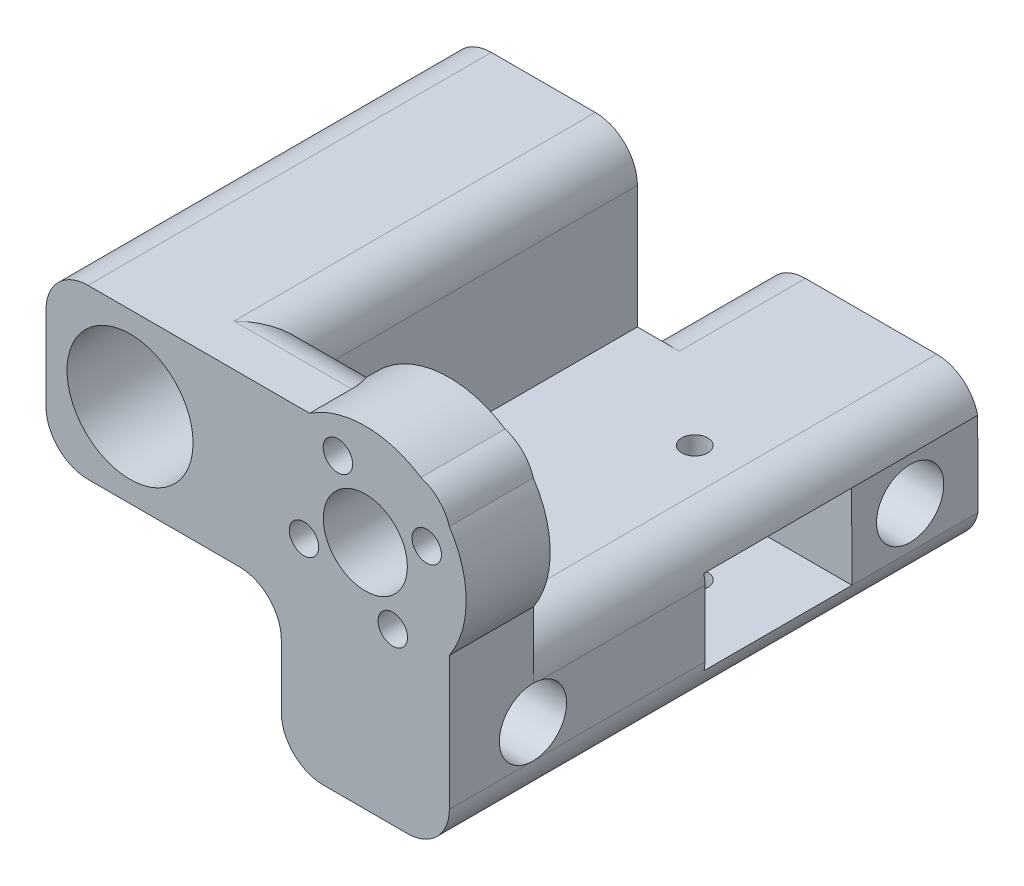
SolidWorks part; units mm, degrees
ref_plane "前视基准面" through (0, 0, 0) normal (0, 0, 1) x (1, 0, 0)
ref_plane "上视基准面" through (0, 0, 0) normal (0, 1, 0) x (1, 0, 0)
ref_plane "右视基准面" through (0, 0, 0) normal (1, 0, 0) x (0, 0, -1)
sketch "草图1" plane through (0, 0, 0) normal (0, 1, 0) x (1, 0, 0)
  line L1 (-10.5078, 7.8964) -> (37.4922, 7.8964)
  line L2 (-10.5078, 7.8964) -> (-10.5078, -40.1036)
  line L3 (-10.5078, -40.1036) -> (37.4922, -40.1036)
  line L4 (37.4922, 7.8964) -> (37.4922, -40.1036)
  line L5 (-10.5078, 7.8964) -> (37.4922, -40.1036) construction
  line L6 (-10.5078, -40.1036) -> (37.4922, 7.8964) construction
  point P4 (13.4922, -16.1036)
  dimension "D1" = 48
  dimension "D2" = 48
extrude "凸台-拉伸1" add sketch "草图1" along normal blind 40
sketch "草图2" plane through (0, 0, 40.1036) normal (0, 0, 1) x (1, 0, 0)
  line L0 (-10.5078, 40) -> (37.4922, 40) construction
  line L1 (-10.5078, 40) -> (-10.5078, 0) construction
  circle A0 centre (-0.5078, 30) radius 7.5
  circle A1 centre (27.4922, 30) radius 5
  circle A2 centre (24.2267, 37.3032) radius 1.75
  circle A3 centre (34.7954, 33.2656) radius 1.75
  circle A4 centre (20.1891, 26.7344) radius 1.75
  circle A5 centre (30.7578, 22.6968) radius 1.75
  dimension "D1" = 15
  dimension "D2" = 10
  dimension "D4" = 10
  dimension "D5" = 10
  dimension "D3" = 28
extrude "切除-拉伸1" cut sketch "草图2" against normal through all
sketch "草图3" plane through (0, 0, 40.1036) normal (0, 0, 1) x (1, 0, 0)
  circle A0 centre (27.4922, 30) radius 12
  circle A1 centre (27.4922, 30) radius 5.5
  circle A2 centre (24.2267, 37.3032) radius 1.75
  circle A3 centre (20.1891, 26.7344) radius 1.75
  circle A4 centre (30.7578, 22.6968) radius 1.75
  circle A5 centre (34.7954, 33.2656) radius 1.75
  dimension "D1" = 24
  dimension "D2" = 11
extrude "凸台-拉伸3" add sketch "草图3" against normal blind 10
sketch "草图4" plane through (0, 0, -7.8964) normal (0, 0, -1) x (-1, 0, 0)
  line L1 (-37.4922, 40) -> (-11.8688, 40)
  line L2 (-37.4922, 40) -> (-37.4922, 20.3994)
  line L3 (-37.4922, 20.3994) -> (-11.8688, 20.3994)
  line L4 (-11.8688, 40) -> (-11.8688, 20.3994)
  line L5 (-37.4922, 40) -> (-11.8688, 20.3994) construction
  line L6 (-37.4922, 20.3994) -> (-11.8688, 40) construction
  point P4 (-24.6805, 30.1997)
extrude "切除-拉伸2" cut sketch "草图4" against normal blind 38
fillet "圆角1" radius 5 1 edges at (37.4922, 40, 35.1036)
sketch "草图5" plane through (37.4922, 0, 0) normal (1, 0, 0) x (0, 0, -1)
  line L1 (-9.6997, 16.5398) -> (10.3003, 16.5398)
  line L2 (-9.6997, 16.5398) -> (-9.6997, 6.5398)
  line L3 (-9.6997, 6.5398) -> (10.3003, 6.5398)
  line L4 (10.3003, 16.5398) -> (10.3003, 6.5398)
  line L5 (-9.6997, 16.5398) -> (10.3003, 6.5398) construction
  line L6 (0.3003, 17.2597) -> (0.3003, 9.8597) construction
  line L18 (-9.6997, 6.5398) -> (10.3003, 16.5398) construction
  point P10 (0.3003, 11.5398)
  dimension "D1" = 10
  dimension "D3" = 20
extrude "切除-拉伸3" cut sketch "草图5" against normal through all
sketch "草图6" plane through (0, 0, 40.1036) normal (0, 0, 1) x (1, 0, 0)
  line L0 (37.4922, 0) -> (37.4922, 2.5)
  line L1 (37.4922, 23.3668) -> (37.4922, 0) construction
  line L2 (-7.5078, 2.5) -> (392.4922, 2.5) construction
  line L3 (37.4922, 2.5) -> (17.4922, 2.5)
  line L4 (17.4922, 2.5) -> (17.4922, 20)
  line L5 (17.4922, 20) -> (-10.5078, 20)
  line L6 (-10.5078, 40) -> (-10.5078, 0) construction
  line L7 (-10.5078, 20) -> (-10.5078, 0)
  line L8 (-10.5078, 0) -> (37.4922, 0)
  dimension "D1" = 20
  dimension "D2" = 20
extrude "切除-拉伸4" cut sketch "草图6" against normal through all
fillet "圆角2" radius 5 7 edges at (16.3639, 40, 30.1036) (11.8688, 40, 11.1036) (37.4922, 2.5, 16.1036) (-10.5078, 40, 16.1036) (-10.5078, 20, 16.1036) (17.4922, 2.5, 16.1036) (17.4922, 20, 16.1036)
sketch "草图7" plane through (17.4922, 0, 0) normal (-1, 0, 0) x (0, 0, 1)
  line L0 (-7.8964, 20) -> (-7.8964, 2.5)
  line L1 (-7.8964, 2.5) -> (1.8729, 2.5)
  line L2 (40.1036, 2.5) -> (-7.8964, 2.5) construction
  line L3 (1.8729, 2.5) -> (1.8729, 20)
  line L4 (40.1036, 20) -> (-7.8964, 20) construction
  line L5 (1.8729, 20) -> (-7.8964, 20)
extrude "凸台-拉伸4" add sketch "草图7" along normal blind 23
fillet "圆角3" radius 5 3 edges at (17.4922, 2.5, -3.0117) (-5.5078, 20, -3.0117) (-5.5078, 2.5, -3.0117)
fillet "圆角4" radius 5 1 edges at (37.4922, 20.3994, 11.1036)
sketch "草图8" plane through (0, 20.3994, 0) normal (0, 1, 0) x (1, 0, 0)
  line L0 (37.3992, -0.9017) -> (17.5853, -0.9017) construction
  line L5 (37.3992, -9.6997) -> (37.3992, 7.8964) construction
  line L6 (17.5853, 7.8964) -> (17.5853, -9.6997) construction
  circle A0 centre (27.4922, -0.9017) radius 1.55
  dimension "D1" = 3.1
extrude "切除-拉伸5" cut sketch "草图8" against normal through all
sketch "草图10" plane through (0, 2.5, 0) normal (0, -1, 0) x (1, 0, 0)
  circle A1 centre (27.4922, 0.9017) radius 1.55
  circle A2 centre (27.4922, 0.9017) radius 4
  dimension "D1" = 8
extrude "凸台-拉伸6" add sketch "草图10" along normal blind 3
sketch "草图11" plane through (0, 0, 1.8729) normal (0, 0, 1) x (1, 0, 0)
  line L0 (12.4922, 2.5) -> (22.4922, 2.5)
  line L1 (22.4922, 2.5) -> (17.4922, 7.5)
  line L2 (17.4922, 7.5) -> (12.4922, 2.5)
  arc A0 (17.4922, 7.5) -> (22.4922, 2.5) centre (22.4922, 7.5) ccw construction
  arc A1 (12.4922, 2.5) -> (17.4922, 7.5) centre (12.4922, 7.5) ccw construction
extrude "凸台-拉伸7" add sketch "草图11" against normal up to surface (9.7692 mm away) up to face at (27.4922, 4.0799, -7.8964)
sketch "草图14" plane through (37.4922, 0, 0) normal (1, 0, 0) x (0, 0, -1)
  circle A0 centre (-30.1576, 11.5) radius 4
  dimension "D1" = 8
extrude "切除-拉伸7" cut sketch "草图14" against normal through all
sketch "草图15" plane through (0, 0, -7.8964) normal (0, 0, -1) x (-1, 0, 0)
  line L0 (-11.8688, 20.3994) -> (-11.8688, 2.5)
  line L1 (-37.3604, 16.5398) -> (-37.3992, 6.5398)
  line L7 (-32.4922, 2.5) -> (0.5078, 2.5)
  line L8 (5.5078, 7.5) -> (5.5078, 16.3397)
  line L9 (10.5078, 25) -> (10.5078, 35)
  line L10 (5.5078, 40) -> (-6.8688, 40)
  line L11 (-11.8688, 35) -> (-11.8688, 20.3994)
  line L12 (-11.8688, 20.3994) -> (-32.4922, 20.3994)
  line L13 (-37.3604, 16.5398) -> (-17.4922, 16.5398)
  line L14 (-32.4922, 2.5) -> (-11.8688, 2.5)
  line L19 (-11.8688, 20.3994) -> (-32.4922, 20.3994)
  line L26 (-17.4922, 16.5398) -> (-17.4922, 7.5)
  line L28 (-17.4922, 7.5) -> (-18.4524, 6.5398)
  line L30 (-18.4524, 6.5398) -> (-37.3992, 6.5398)
  arc A7 (0.5078, 2.5) -> (5.5078, 7.5) centre (0.5078, 7.5) ccw
  arc A8 (8.0078, 20.6699) -> (5.5078, 16.3397) centre (10.5078, 16.3397) ccw
  arc A9 (8.0078, 20.6699) -> (10.5078, 25) centre (5.5078, 25) ccw
  arc A10 (10.5078, 35) -> (5.5078, 40) centre (5.5078, 35) ccw
  arc A11 (-6.8688, 40) -> (-11.8688, 35) centre (-6.8688, 35) ccw
  arc A12 (-32.4922, 20.3994) -> (-37.3604, 16.5398) centre (-32.4922, 15.3994) ccw
  arc A13 (-37.3992, 6.5398) -> (-32.4922, 2.5) centre (-32.4922, 7.5) ccw
  arc A19 (-32.4922, 20.3994) -> (-37.3604, 16.5398) centre (-32.4922, 15.3994) ccw
  arc A20 (-37.3992, 6.5398) -> (-32.4922, 2.5) centre (-32.4922, 7.5) ccw
  dimension "D1" = 0
extrude "凸台-拉伸8" add sketch "草图15" along normal blind 15
fillet "圆角6" radius 5 2 edges at (11.8688, 20.3994, -15.3964) (11.8688, 2.5, -15.3964)
sketch "草图16" plane through (37.4922, 0, 0) normal (1, 0, 0) x (0, 0, -1)
  circle A0 centre (14.8424, 11.5) radius 4
extrude "切除-拉伸8" cut sketch "草图16" against normal through all
